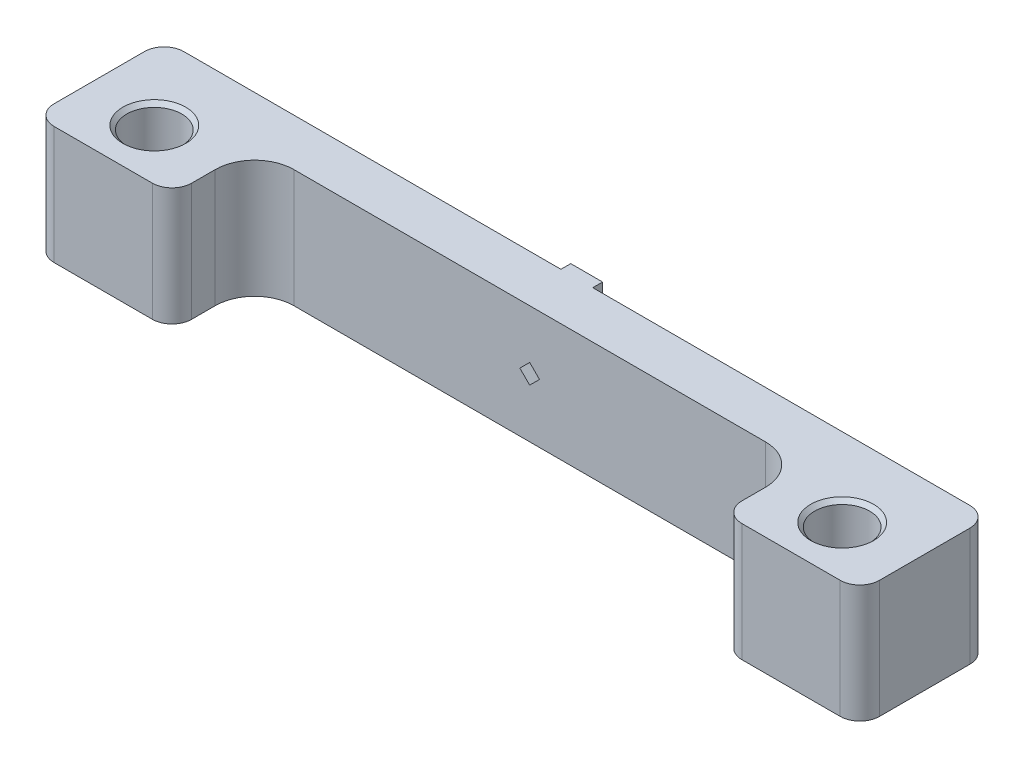
SolidWorks part; units mm, degrees
ref_plane "Ebene vorne" through (0, 0, 0) normal (0, 0, 1) x (1, 0, 0)
ref_plane "Ebene oben" through (0, 0, 0) normal (0, 1, 0) x (1, 0, 0)
ref_plane "Ebene rechts" through (0, 0, 0) normal (1, 0, 0) x (0, 0, -1)
sketch "Skizze1" plane through (0, 0, 0) normal (0, 1, 0) x (1, 0, 0)
  line L0 (-91.0599, 0) -> (138.7496, 0) construction
  line L1 (-105, 0) -> (-105, -13)
  line L2 (-105, 0) -> (-105, 20)
  line L3 (-105, 20) -> (105, 20)
  line L4 (105, 0) -> (105, 20)
  line L5 (-105, -13) -> (-70, -13)
  line L6 (105, -13) -> (105, 0)
  line L7 (0, 39.9859) -> (0, -26.2006) construction
  line L8 (-70, -13) -> (-70, 8)
  line L9 (-70, 8) -> (70, 8)
  line L10 (70, -13) -> (70, 8)
  line L11 (70, -13) -> (105, -13)
  point P0 (0, 0)
  point P17 (0, 8)
  dimension "D4" = 35
  dimension "D1" = 105
  dimension "D2" = 20
  dimension "D3" = 13
  dimension "D5" = 12
  dimension "D6" = 105
extrude "Aufsatz-Linear austragen1" add sketch "Skizze1" along normal blind 30
sketch "Skizze2" plane through (0, 30, 0) normal (0, 1, 0) x (1, 0, 0)
  line L0 (0, 39.3394) -> (0, -28.0733) construction
  line L1 (-59.9066, 0) -> (57.7327, 0) construction
  circle A0 centre (-87.5, 0) radius 7
  circle A1 centre (87.5, 0) radius 7
  dimension "D2" = 14
  dimension "D1" = 175
  dimension "D3" = 0
extrude "Schnitt-Linear austragen1" cut sketch "Skizze2" against normal offset from surface (20 mm away) 10 up to face at (0, 0, -0.5)
sketch "Skizze5" plane through (0, 0, -20) normal (0, 0, -1) x (-1, 0, 0)
  line L0 (-105, 30) -> (105, 30) construction
  line L1 (0, 49.8648) -> (0, -19.3679) construction
  line L2 (-4.05, 0) -> (-4.05, 30)
  line L3 (-4.05, 30) -> (4.05, 30)
  line L4 (4.05, 0) -> (4.05, 30)
  line L5 (-4.05, 0) -> (4.05, 0)
  line L6 (-105, 0) -> (105, 0) construction
  line L7 (0, 16.5001) -> (0, -16.5001) construction
  point P10 (0, 30)
  point P13 (4.05, 15)
  point P14 (-4.05, 15)
  dimension "D2" = 8.1
extrude "Aufsatz-Linear austragen2" add sketch "Skizze5" along normal blind 3
chamfer "Fase2" distance 0.5 angle 45 4 edges at (-4.05, 15, -23) (0, 0, -23) (4.05, 15, -23) (0, 30, -23)
chamfer "Fase1" distance 1 angle 45 2 edges at (87.5, 30, -7) (-87.5, 30, 7)
fillet "Verrundung1" radius 5 6 edges at (-70, 15, 13) (-105, 15, 13) (105, 15, -20) (-105, 15, -20) (105, 15, 13) (70, 15, 13)
fillet "Verrundung2" radius 10 2 edges at (70, 15, -8) (-70, 15, -8)
sketch "Skizze8" plane through (0, 0, 0) normal (0, 1, 0) x (1, 0, 0)
  line L0 (0, -30.583) -> (0, 45.0788) construction
  circle A0 centre (87.5, 0) radius 2.5
  circle A1 centre (-87.5, 0) radius 2.5
  dimension "D1" = 5
extrude "Schnitt-Linear austragen2" cut sketch "Skizze8" along normal up to next
sketch "Skizze9" plane through (0, 0, -8) normal (0, 0, 1) x (1, 0, 0)
  line L0 (0, 53.9537) -> (0, -20.781) construction
  line L1 (-26.3437, 0) -> (23.6468, 0) construction
  line L2 (-60, 0) -> (60, 0) construction
  line L3 (0, 17.5) -> (-2.5, 15)
  line L4 (-2.5, 15) -> (0, 12.5)
  line L5 (0, 12.5) -> (2.5, 15)
  line L6 (2.5, 15) -> (0, 17.5)
  circle A0 centre (0, 15) radius 2.5 construction
  dimension "D1" = 5
  dimension "D2" = 15
extrude "Schnitt-Linear austragen3" cut sketch "Skizze9" against normal through all
ref_axis "Achse1" through (0, -24.5177, 0) along (0, 1, 0)
